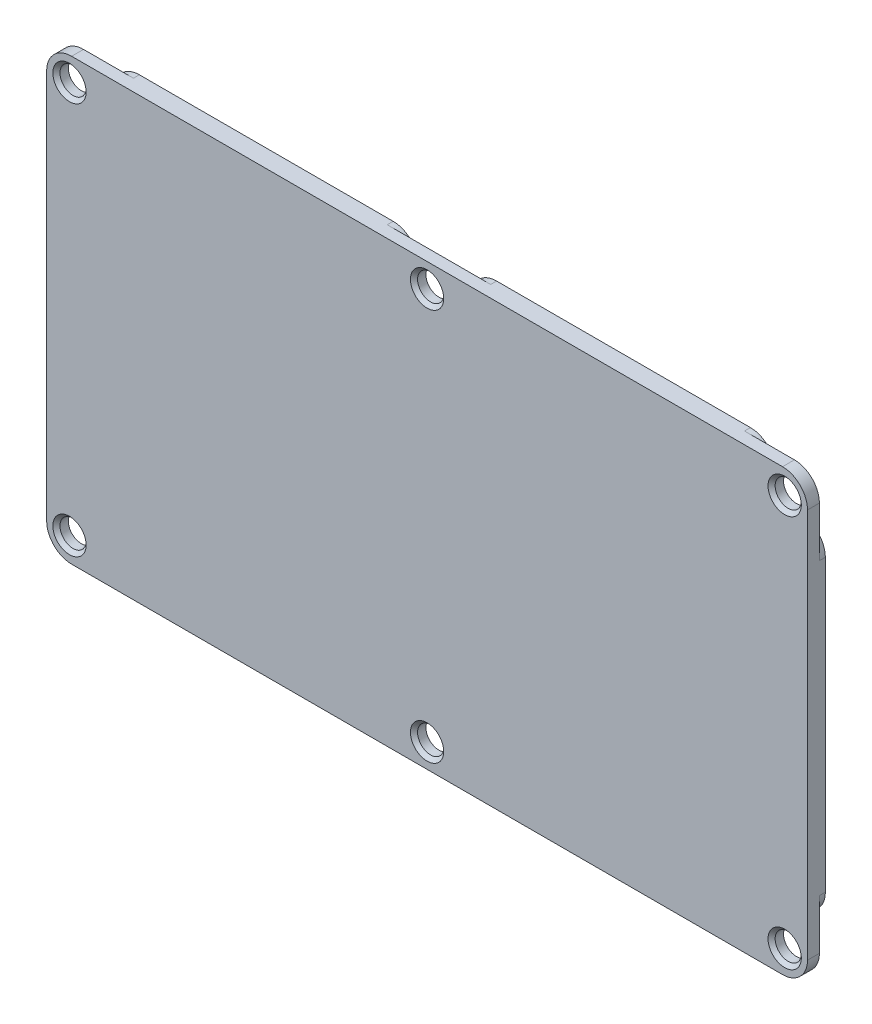
SolidWorks part; units mm, degrees
ref_plane "정면" through (0, 0, 0) normal (0, 0, 1) x (1, 0, 0)
ref_plane "윗면" through (0, 0, 0) normal (0, 1, 0) x (1, 0, 0)
ref_plane "우측면" through (0, 0, 0) normal (1, 0, 0) x (0, 0, -1)
sketch "스케치1" plane through (0, 0, 0) normal (0, 0, 1) x (1, 0, 0)
  line L1 (-32, -18.5) -> (32, -18.5)
  line L2 (-32, -18.5) -> (-32, 18.5)
  line L3 (-32, 18.5) -> (32, 18.5)
  line L4 (32, -18.5) -> (32, 18.5)
  line L5 (-32, -18.5) -> (32, 18.5) construction
  line L6 (-32, 18.5) -> (32, -18.5) construction
  point P0 (0, 0)
  dimension "D1" = 37
  dimension "D2" = 64
extrude "보스-돌출1" add sketch "스케치1" along normal blind 1
sketch "스케치2" plane through (0, 0, 0) normal (0, 0, -1) x (-1, 0, 0)
  line L1 (-32, 14.3) -> (32, 14.3)
  line L2 (-32, 14.3) -> (-32, -14.3)
  line L3 (-32, -14.3) -> (32, -14.3)
  line L4 (32, 14.3) -> (32, -14.3)
  line L5 (-32, 14.3) -> (32, -14.3) construction
  line L6 (-32, -14.3) -> (32, 14.3) construction
  line L7 (-27.8, 18.5) -> (-2.25, 18.5)
  line L8 (-27.8, 18.5) -> (-27.8, -18.5)
  line L9 (-27.8, -18.5) -> (-2.25, -18.5)
  line L10 (-2.25, 18.5) -> (-2.25, -18.5)
  line L11 (-27.8, 18.5) -> (-2.25, -18.5) construction
  line L12 (-27.8, -18.5) -> (-2.25, 18.5) construction
  line L13 (2.25, 18.5) -> (27.8, 18.5)
  line L14 (2.25, 18.5) -> (2.25, -18.5)
  line L15 (2.25, -18.5) -> (27.8, -18.5)
  line L16 (27.8, 18.5) -> (27.8, -18.5)
  line L17 (2.25, 18.5) -> (27.8, -18.5) construction
  line L18 (2.25, -18.5) -> (27.8, 18.5) construction
  line L20 (-32, 18.5) -> (32, 18.5) construction
  line L21 (32, -18.5) -> (-32, -18.5) construction
  line L22 (-32, -18.5) -> (-32, 18.5) construction
  point P0 (0, 0)
  point P6 (-15.025, 0)
  point P11 (15.025, 0)
  line M13 (-32, 18.5) -> (-32, -18.5)
  line M14 (-32, -18.5) -> (32, -18.5)
  line M15 (32, -18.5) -> (32, 18.5)
  line M16 (32, 18.5) -> (-32, 18.5)
  dimension "D1" = 4.2
  dimension "D2" = 4.5
  dimension "D3" = 4.2
  dimension "D4" = 4.2
extrude "보스-돌출2" add sketch "스케치2" along normal blind 0.5 contours L8 L1 L3 M13 | L10 L1 L8 L3 | L10 L8 L1 M16 | L10 L3 L8 M14 | L16 L1 L14 L3 | L16 L14 L1 M16 | L14 L1 L10 L3 | L1 L16 L3 M15 | L16 L3 L14 M14
fillet "필렛1" radius 2.1 32 edges at (32, -18.5, 0.5) (27.8, -14.3, -0.25) (32, -14.3, -0.25) (-2.25, -14.3, -0.25) (2.25, -14.3, -0.25) (-32, -14.3, -0.25) (-27.8, -14.3, -0.25) (27.8, -16.4, 0) (27.8, -18.5, -0.25) (27.8, 16.4, 0) (27.8, 14.3, -0.25) (27.8, 18.5, -0.25) (-2.25, -16.4, 0) (-2.25, -18.5, -0.25) (-2.25, 16.4, 0) (-2.25, 14.3, -0.25) (-2.25, 18.5, -0.25) (2.25, -16.4, 0) (2.25, -18.5, -0.25) (2.25, 16.4, 0) (2.25, 18.5, -0.25) (2.25, 14.3, -0.25) (-27.8, -16.4, 0) (-27.8, -18.5, -0.25) (-27.8, 16.4, 0) (-27.8, 18.5, -0.25) (-27.8, 14.3, -0.25) (-32, -18.5, 0.5) (-32, 18.5, 0.5) (-32, 14.3, -0.25) (32, 14.3, -0.25) (32, 18.5, 0.5)
sketch "스케치3" plane through (0, 0, 1) normal (0, 0, 1) x (1, 0, 0)
  line L5 (-30.08, -16.5) -> (30.08, -16.5) construction
  line L6 (-30.08, -16.5) -> (-30.08, 16.5) construction
  line L7 (-30.08, 16.5) -> (30.08, 16.5) construction
  line L8 (30.08, -16.5) -> (30.08, 16.5) construction
  line L9 (-30.08, -16.5) -> (30.08, 16.5) construction
  line L10 (-30.08, 16.5) -> (30.08, -16.5) construction
  circle A4 centre (-30.08, 16.5) radius 1.1
  circle A5 centre (0, 16.5) radius 1.1
  circle A6 centre (30.08, 16.5) radius 1.1
  circle A7 centre (30.08, -16.5) radius 1.1
  circle A8 centre (-30.08, -16.5) radius 1.1
  circle A10 centre (0, -16.5) radius 1.1
  point P0 (0, 0)
  dimension "D3" = 2.2
  dimension "D1" = 60.16
  dimension "D2" = 33
extrude "컷-돌출1" cut sketch "스케치3" against normal up to next
chamfer "모따기1" distance 0.3 angle 45 6 edges at (31.18, -16.5, 1) (1.1, -16.5, 1) (-28.98, -16.5, 1) (31.18, 16.5, 1) (1.1, 16.5, 1) (-28.98, 16.5, 1)
